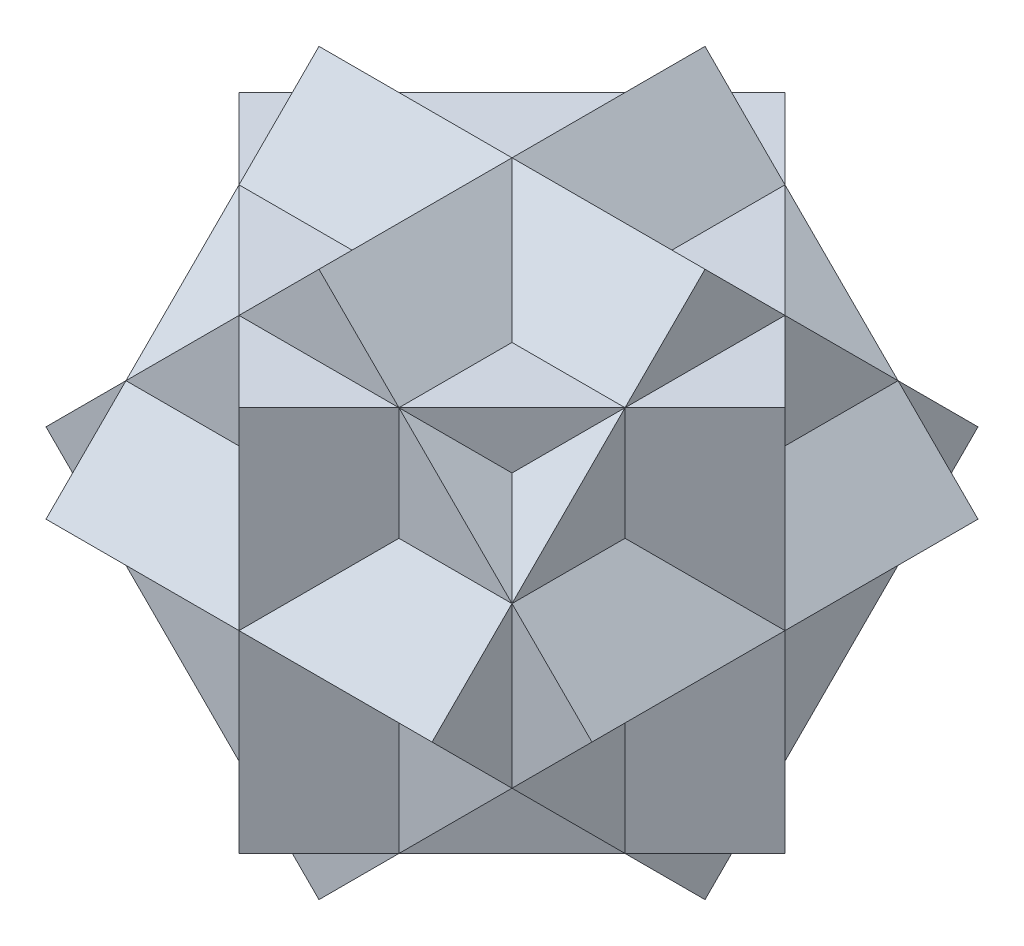
SolidWorks part; units mm, degrees
ref_plane "Front Plane" through (0, 0, 0) normal (0, 0, 1) x (1, 0, 0)
ref_plane "Top Plane" through (0, 0, 0) normal (0, 1, 0) x (1, 0, 0)
ref_plane "Right Plane" through (0, 0, 0) normal (1, 0, 0) x (0, 0, -1)
sketch "Sketch3" plane through (0, 0, 0) normal (0, 0, 1) x (1, 0, 0)
  line L0 (-155.1461, 0) -> (0, 155.1461)
  line L1 (-155.1461, 0) -> (0, -155.1461)
  line L2 (0, 155.1461) -> (155.1461, 0)
  line L3 (0, -155.1461) -> (155.1461, 0)
  line L4 (-155.1461, 0) -> (155.1461, 0) construction
  line L5 (0, 155.1461) -> (0, -155.1461) construction
  point P1 (0, 0)
  dimension "D1" = 219.4098
sketch "Sketch4" plane through (0, 0, 0) normal (0, 1, 0) x (1, 0, 0)
  line L0 (-155.1461, 0) -> (0, 155.1461)
  line L1 (-155.1461, 0) -> (0, -155.1461)
  line L2 (0, 155.1461) -> (155.1461, 0)
  line L3 (0, -155.1461) -> (155.1461, 0)
  line L4 (-155.1461, 0) -> (155.1461, 0) construction
  line L5 (0, 155.1461) -> (0, -155.1461) construction
  point P1 (0, 0)
sketch "Sketch5" plane through (0, 0, 0) normal (1, 0, 0) x (0, 0, -1)
  line L0 (-155.1461, 0) -> (0, 155.1461)
  line L1 (-155.1461, 0) -> (0, -155.1461)
  line L2 (0, 155.1461) -> (155.1461, 0)
  line L3 (0, -155.1461) -> (155.1461, 0)
  line L4 (-155.1461, 0) -> (155.1461, 0) construction
  line L5 (0, 155.1461) -> (0, -155.1461) construction
  line L6 (0, 155.1461) -> (0, -155.1461) construction
  point P1 (0, 0)
extrude "Boss-Extrude1" add sketch "Sketch3" along normal mid plane 219.4098
extrude "Boss-Extrude2" add sketch "Sketch4" along normal mid plane 219.4098
extrude "Boss-Extrude3" add sketch "Sketch5" along normal mid plane 219.4098
equation "\"side_length\"= 4 * 2.238285 - 2 * \"Subtract\""
equation "\"D1@Sketch3\"=\"side_length\""
equation "\"D1@Boss-Extrude1\"=\"side_length\""
equation "\"D1@Boss-Extrude2\"=\"side_length\""
equation "\"D1@Boss-Extrude3\"=\"side_length\""
equation "\"Joiner_spacing\"= 0.1"
equation "\"Subtract\"= 4mm"
